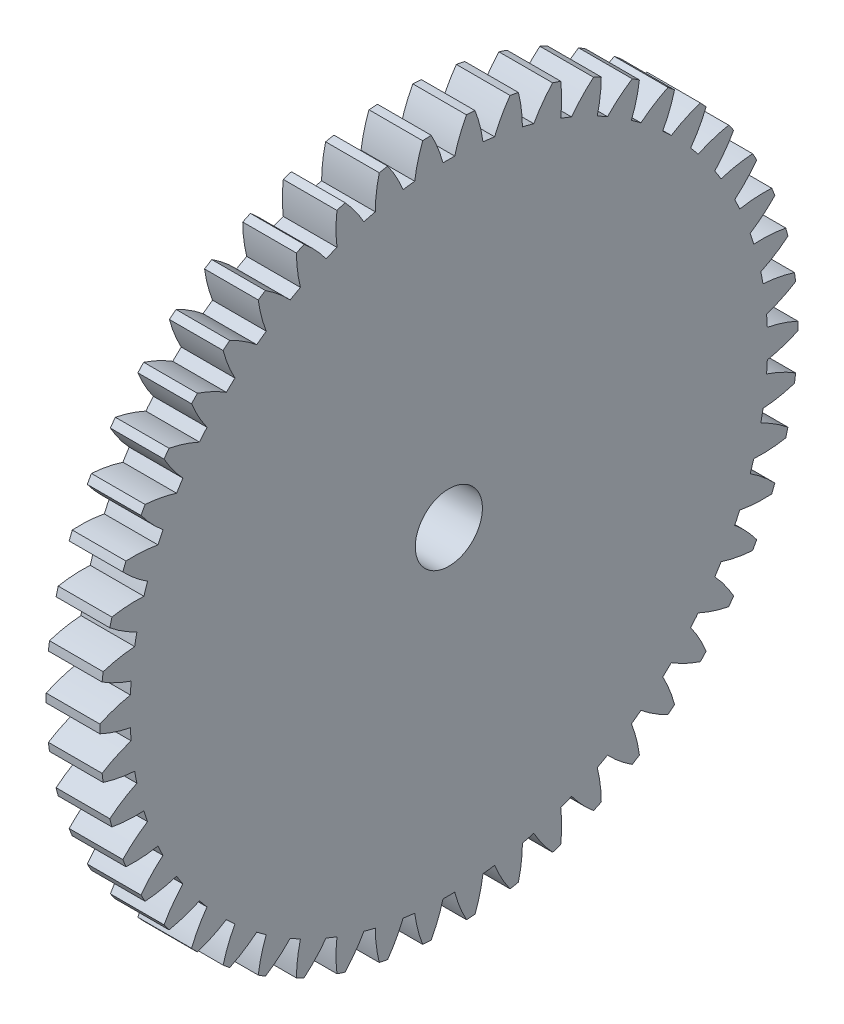
SolidWorks part; units mm, degrees
ref_plane "Plane1" through (0, 0, 0) normal (0, 0, 1) x (1, 0, 0)
ref_plane "Plane2" through (0, 0, 0) normal (0, 1, 0) x (1, 0, 0)
ref_plane "Plane3" through (0, 0, 0) normal (1, 0, 0) x (0, 0, -1)
sketch "HoldingSke" plane through (0, 0, 0) normal (0, 1, 0) x (1, 0, 0)
  line L0 (0, 0) -> (0.6428, -0.766)
  line L1 (-15, 0) -> (100, 0) construction
  line L2 (0, 0) -> (-2.1039, 2.3779)
  line L3 (0, 0) -> (-11.863, 4.5341)
  line L4 (0, 0) -> (5.5511, 6.6156)
  line L5 (0, 0) -> (-46.8476, -17.4728)
  line L6 (0, 0) -> (-3.3159, -2.2372)
  line L7 (-2.1039, 2.3779) -> (8.6586, 51.2059)
  line L8 (-76.2, 54.61) -> (-75.3, 54.61)
  line L9 (-71.009, 38.7566) -> (-53.1078, 45.2721)
  line L10 (-76.2, 71.12) -> (104.1128, 71.12)
  line L11 (0, 0) -> (-4, 0)
  line L12 (-76.2, 101.6) -> (-76.162, 101.6)
  line L13 (24.9733, 27.94) -> (52.9518, 28.4284)
  line L14 (24.9733, 27.94) -> (24.9743, 27.94)
  line L15 (24.9733, 27.94) -> (100.4006, 29.5858)
  line L16 (-63.627, -1) -> (-12.827, -1)
  circle A0 centre (0, 0) radius 2.5
  circle A1 centre (0, 0) radius 23.749
  circle A2 centre (0, 0) radius 37.5
  circle A3 centre (0, 0) radius 2.5
  dimension "Num_teeth" = 50
  dimension "Pitch_radius" = 180.3128
  dimension "Width" = 4
  dimension "Thickness" = 4
sketch "BasProSke" plane through (0, 0, 0) normal (0, 1, 0) x (1, 0, 0)
  line L0 (-10, 0) -> (60, 0) construction
  line L1 (0, 0) -> (0, 26)
  line L2 (0, 0) -> (4, 0)
  line L3 (4, 0) -> (4, 26)
  line L4 (4, 26) -> (0, 26)
  dimension "Thickness" = 4
  dimension "Diameter" = 52
revolve "Base-Revolve" add sketch "BasProSke" angle 360 about L0
sketch "TooCutSke" plane through (0, 0, 0) normal (1, 0, 0) x (0, 0, -1)
  line L1 (0, 0) -> (0, 107) construction
  line L2 (0, 0) -> (-0.8518, 24.9855) construction
  line L3 (0, 0) -> (-3.1382, 49.8807) construction
  line L4 (-0.8518, 24.9855) -> (-1.5691, 24.9404) construction
  arc A0 (0.4377, 23.745) -> (-0.4377, 23.745) centre (0, 0) ccw
  arc A1 (1.3294, 25.9914) -> (-1.3294, 25.9914) centre (0, 0) ccw
  circle A2 centre (0, 0) radius 25 construction
  circle A3 centre (0, 0) radius 23.4923 construction
  arc A4 (-0.4377, 23.745) -> (-1.3294, 25.9914) centre (-10.1099, 21.2056) ccw
  arc A5 (1.3294, 25.9914) -> (0.4377, 23.745) centre (10.1099, 21.2056) ccw
extrude "ToothCut" cut sketch "TooCutSke" along normal through all
fillet "Breaks" [suppressed] radius 0.02 tangent propagation no
fillet "RootFillets" [suppressed] radius 0.251
pattern_circular "TeethCuts" count 50 every 7.2 about axis through (-10, 0, 0) along (1, 0, 0) of "ToothCut", "RootFillets", "Breaks"
sketch "HubNeaOneSke" plane through (0, 0, 0) normal (-1, 0, 0) x (0, 0, 1)
  circle A0 centre (0, 0) radius 23.749
  dimension "Diameter" = 47.498
extrude "HubNearOne" [suppressed] add sketch "HubNeaOneSke" along normal blind 46.0001
sketch "HubNeaBotSke" plane through (0, 0, 0) normal (-1, 0, 0) x (0, 0, 1)
  circle A0 centre (0, 0) radius 23.749
  dimension "Diameter" = 47.498
extrude "HubNearBoth" [suppressed] add sketch "HubNeaBotSke" along normal blind 23
ref_plane "FarPln" through (4, 0, 0) normal (1, 0, 0) x (0, 0, -1)
sketch "HubFarSke" plane through (4, 0, 0) normal (1, 0, 0) x (0, 0, -1)
  circle A0 centre (0, 0) radius 23.749
  dimension "Diameter" = 47.498
extrude "HubFar" [suppressed] add sketch "HubFarSke" along normal blind 23
sketch "BorSke" plane through (0, 0, 0) normal (1, 0, 0) x (0, 0, -1)
  circle A0 centre (0, 0) radius 2.5
  dimension "Diameter" = 5
extrude "Bore" cut sketch "BorSke" along normal mid plane 100.0001
sketch "KeySke" plane through (0, 0, 0) normal (1, 0, 0) x (0, 0, -1)
  line L0 (-1, 0) -> (-1, 3.4)
  line L1 (-1, 3.4) -> (1, 3.4)
  line L2 (1, 3.4) -> (1, 0)
  line L3 (0, 0) -> (0, 34) construction
  line L4 (-1, 0) -> (1, 0)
  dimension "Width" = 2
extrude "Keyway" [suppressed] cut sketch "KeySke" along normal mid plane 100.0001
pattern_circular "Keyway2" [suppressed] count 2 every 90 about axis through (-10, 0, 0) along (1, 0, 0) reverse direction yes
equation "' \"Module@HoldingSke\" = 6.35"
equation "' \"Num_teeth@HoldingSke\" = 12"
equation "' \"Ap@HoldingSke\" =  20"
equation "' \"Ap@HoldingSke\" = 20"
equation "' \"Width@HoldingSke\" = 0.5 * 25.4"
equation "' \"Hub_dia@HoldingSke\"= 1 * 25.4"
equation "' \"Hub_dia@HoldingSke\" = 1 * 25.4"
equation "' \"Overall_len@HoldingSke\" = 1.0 * 25.4"
equation "' \"Bore@HoldingSke\" = 0.75 * 25.4"
equation "' \"T_dim@HoldingSke\" = 0.1 * 25.4"
equation "' \"Width@KeySke\" = 0.25 * 25.4"
equation "' \"Show_teeth@HoldingSke\" = 13"
equation "' \"Backlash@HoldingSke\" = 0.009 * 25.4"
equation "' \"Addendum_fac@HoldingSke\" = 1.0"
equation "' \"Dedendum_fac@HoldingSke\" = 1.25"
equation "' \"Dedendum_add@HoldingSke\" = 0.00005 * 25.4"
equation "' \"Clearance_fac@HoldingSke\" = 0.25"
equation "\"Pitch@HoldingSke\" = 1 / \"Module@HoldingSke\""
equation "\"Overcut_dia@TooCutSke\" = (\"Num_teeth@HoldingSke\" + 2 * \"Addendum_fac@HoldingSke\") / \"Pitch@HoldingSke\" + 0.002 * 25.4"
equation "\"Pitch_dia@TooCutSke\" = \"Num_teeth@HoldingSke\" / \"Pitch@HoldingSke\""
equation "\"Base_dia@TooCutSke\" = \"Num_teeth@HoldingSke\" / \"Pitch@HoldingSke\" * cos((\"Ap@HoldingSke\"  * 3.14159265 / 180))"
equation "\"Root_dia@TooCutSke\" = (\"Num_teeth@HoldingSke\" + 2) / \"Pitch@HoldingSke\" - 2 * (\"Addendum_fac@HoldingSke\" + \"Dedendum_fac@HoldingSke\") / \"Pitch@HoldingSke\" - \"Dedendum_add@HoldingSke\" * 2"
equation "\"Half_ang@TooCutSke\" = 180 / \"Num_teeth@HoldingSke\""
equation "\"Half_CT@TooCutSke\" = \"Num_teeth@HoldingSke\" / \"Pitch@HoldingSke\" * sin((3.14159265 / 2 / \"Num_teeth@HoldingSke\")) / 2 - 7 * \"Backlash@HoldingSke\" / 4"
equation "\"Flank_rad@TooCutSke\" = \"Num_teeth@HoldingSke\" / \"Pitch@HoldingSke\" / 5"
equation "\"Radius@RootFillets\" = \"Clearance_fac@HoldingSke\" / \"Pitch@HoldingSke\" + \"Dedendum_add@HoldingSke\""
equation "\"Break_rad@Breaks\" = 0.02 / \"Pitch@HoldingSke\""
equation "\"Thickness@HoldingSke\" = \"Width@HoldingSke\""
equation "\"OAL@HoldingSke\" = \"Thickness@HoldingSke\""
equation "\"MHD@HoldingSke\" = (\"Num_teeth@HoldingSke\" + 2) / \"Pitch@HoldingSke\" - 2 * (\"Addendum_fac@HoldingSke\" + \"Dedendum_fac@HoldingSke\")  / \"Pitch@HoldingSke\" - \"Dedendum_add@HoldingSke\" * 2"
equation "\"MBD@HoldingSke\" = (\"Num_teeth@HoldingSke\" + 2) / \"Pitch@HoldingSke\" - 2 * (\"Addendum_fac@HoldingSke\" + \"Dedendum_fac@HoldingSke\")  / \"Pitch@HoldingSke\" - \"Dedendum_add@HoldingSke\" * 2 - 0.002 * 25.4"
equation "\"MHD@HoldingSke\" = ((sgn( \"MHD@HoldingSke\" - \"Hub_dia@HoldingSke\" )-1)*( \"MHD@HoldingSke\" - \"Hub_dia@HoldingSke\" ))/-2+ \"Hub_dia@HoldingSke\""
equation "\"MBD@HoldingSke\" = ((sgn( \"MBD@HoldingSke\" - \"Bore@HoldingSke\" )-1)*( \"MBD@HoldingSke\" - \"Bore@HoldingSke\" ))/-2+ \"Bore@HoldingSke\""
equation "\"OAL@HoldingSke\" = ((sgn( \"OAL@HoldingSke\" - \"Overall_len@HoldingSke\" )+1)*( \"OAL@HoldingSke\" - \"Overall_len@HoldingSke\" ))/2 + \"Overall_len@HoldingSke\" + 0.000002 * 25.4"
equation "\"Num_teeth@TeethCuts\" = int( \"Show_teeth@HoldingSke\" ) + 1"
equation "\"Num_teeth@TeethCuts\" = ((sgn( \"Num_teeth@TeethCuts\" - \"Num_teeth@HoldingSke\" )-1)*( \"Num_teeth@TeethCuts\" - \"Num_teeth@HoldingSke\" ))/-2+ \"Num_teeth@HoldingSke\""
equation "\"Num_teeth@TeethCuts\" = ((sgn( \"Num_teeth@TeethCuts\" - 2.0)+1)*( \"Num_teeth@TeethCuts\" - 2.0))/2 +2.0"
equation "\"Angle@TeethCuts\" = 360.0 / \"Num_teeth@HoldingSke\""
equation "\"Diameter@BasProSke\" = (\"Num_teeth@HoldingSke\" + 2 * \"Addendum_fac@HoldingSke\") / \"Pitch@HoldingSke\""
equation "\"Thickness@BasProSke\"  = \"Thickness@HoldingSke\""
equation "' \"Fillet_rad@BasProSke\" =  \"Thickness@HoldingSke\" * 0.05"
equation "' \"Fillet_rad@BasProSke\" = \"Thickness@HoldingSke\" * 0.05"
equation "\"MHD@HoldingSke\" = ((sgn( \"MHD@HoldingSke\" - \"Root_dia@TooCutSke\" )-1)*( \"MHD@HoldingSke\" - \"Root_dia@TooCutSke\" ))/-2+ \"Root_dia@TooCutSke\""
equation "\"Diameter@HubNeaOneSke\" = \"MHD@HoldingSke\""
equation "\"Length@HubNearOne\" = \"OAL@HoldingSke\" - \"Thickness@BasProSke\""
equation "\"Diameter@HubNeaBotSke\" = \"MHD@HoldingSke\""
equation "\"Length@HubNearBoth\" = ( \"OAL@HoldingSke\" - \"Thickness@BasProSke\" ) / 2.0"
equation "\"Thickness@FarPln\" = \"Thickness@BasProSke\""
equation "\"Diameter@HubFarSke\" = \"MHD@HoldingSke\""
equation "\"Length@HubFar\" = ( \"OAL@HoldingSke\" - \"Thickness@BasProSke\" ) / 2.0"
equation "\"Diameter@BorSke\" = \"MBD@HoldingSke\""
equation "\"D1@Bore\" = \"OAL@HoldingSke\" * 2.0"
equation "\"D1@Keyway\" = \"OAL@HoldingSke\" * 2.0"
equation "\"Offset@KeySke\" = \"T_dim@HoldingSke\" + \"MBD@HoldingSke\" / 2.0"
